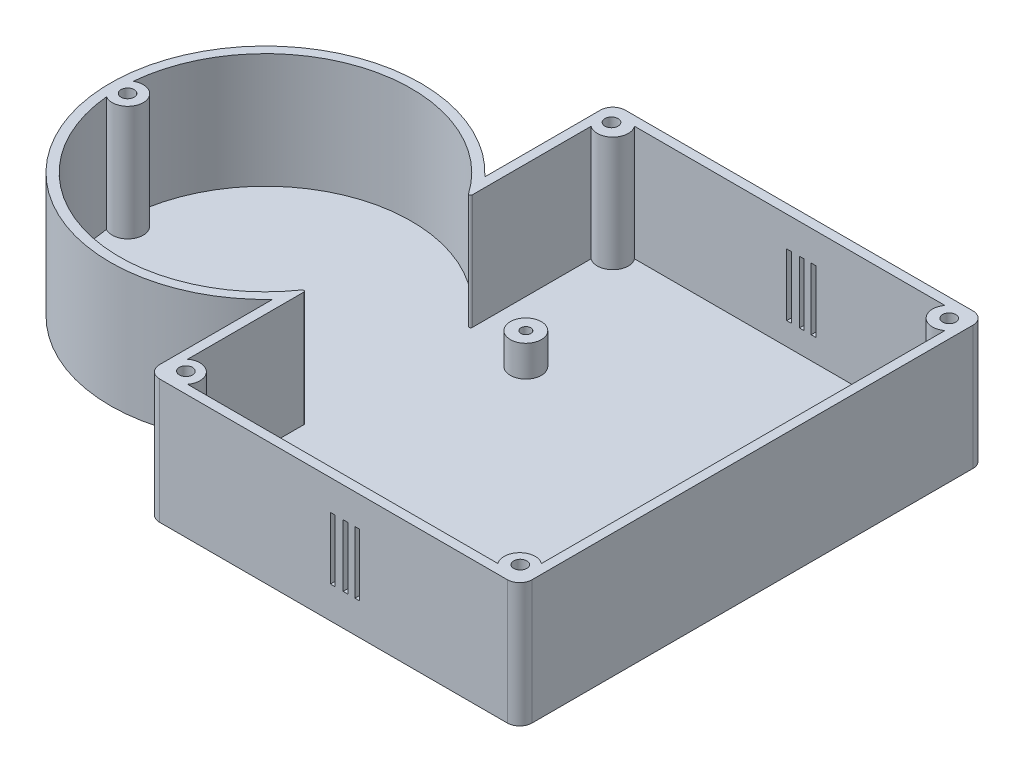
SolidWorks part; units mm, degrees
ref_plane "Front Plane" through (0, 0, 0) normal (0, 0, 1) x (1, 0, 0)
ref_plane "Top Plane" through (0, 0, 0) normal (0, 1, 0) x (1, 0, 0)
ref_plane "Right Plane" through (0, 0, 0) normal (1, 0, 0) x (0, 0, -1)
sketch "Sketch1" plane through (0, 0, 0) normal (0, 1, 0) x (1, 0, 0)
  line L0 (240.8148, 785.6528) -> (1635.5674, 785.6528) construction
sketch "Sketch8" plane through (0, 0, 0) normal (0, 1, 0) x (1, 0, 0)
  line L1 (13.7089, 147.1642) -> (133.7089, 147.1642)
  line L2 (13.7089, 147.1642) -> (13.7089, -2.8358)
  line L3 (13.7089, -2.8358) -> (133.7089, -2.8358)
  line L4 (133.7089, 147.1642) -> (133.7089, -2.8358)
  line L5 (13.7089, 147.1642) -> (133.7089, -2.8358) construction
  line L6 (13.7089, -2.8358) -> (133.7089, 147.1642) construction
  arc A0 (13.7103, 107.7112) -> (14.0464, 36.6131) centre (-21.2814, 71.9959) ccw
  point P0 (73.7089, 72.1642)
  point P5 (73.6501, 72.2835)
  point P6 (-21.2911, 72.0742)
  dimension "D1" = 120
  dimension "D2" = 150
  dimension "D3" = 95
extrude "Boss-Extrude3" add sketch "Sketch8" along normal blind 40 contours L1 L4 L3 L2
sketch "Sketch9" plane through (0, 0, 0) normal (0, 1, 0) x (1, 0, 0)
  circle A0 centre (-22.779, 71.7485) radius 50
extrude "Boss-Extrude4" add sketch "Sketch9" along normal blind 40
shell "Shell1" thickness 3 removed face at (39.2942, 40, -72.0256)
sketch "Sketch11" plane through (0, 0, 0) normal (0, 0, 1) x (1, 0, 0)
  line L5 (72.7415, 30.2907) -> (74.2415, 30.2907)
  line L6 (72.7415, 30.2907) -> (72.7415, 10.2907)
  line L7 (72.7415, 10.2907) -> (74.2415, 10.2907)
  line L8 (74.2415, 30.2907) -> (74.2415, 10.2907)
  line L9 (72.7415, 30.2907) -> (74.2415, 10.2907) construction
  line L10 (72.7415, 10.2907) -> (74.2415, 30.2907) construction
  point P0 (73.4915, 20.2907)
  dimension "D1" = 20
  dimension "D2" = 1.5
sketch "Sketch12" plane through (0, 0, 2.8358) normal (0, 0, 1) x (1, 0, 0)
  line L1 (76.8389, 30.2907) -> (78.3389, 30.2907)
  line L2 (76.8389, 30.2907) -> (76.8389, 10.2907)
  line L3 (76.8389, 10.2907) -> (78.3389, 10.2907)
  line L4 (78.3389, 30.2907) -> (78.3389, 10.2907)
  line L5 (76.8389, 30.2907) -> (78.3389, 10.2907) construction
  line L6 (76.8389, 10.2907) -> (78.3389, 30.2907) construction
  point P0 (77.5889, 20.2907)
  dimension "D1" = 20
  dimension "D2" = 1.5
sketch "Sketch15" plane through (0, 0, 0) normal (0, 0, 1) x (1, 0, 0)
  line L1 (80.6291, 30.2907) -> (82.1291, 30.2907)
  line L2 (80.6291, 30.2907) -> (80.6291, 10.2907)
  line L3 (80.6291, 10.2907) -> (82.1291, 10.2907)
  line L4 (82.1291, 30.2907) -> (82.1291, 10.2907)
  line L5 (80.6291, 30.2907) -> (82.1291, 10.2907) construction
  line L6 (80.6291, 10.2907) -> (82.1291, 30.2907) construction
  point P0 (81.3791, 20.2907)
  dimension "D1" = 1.5
  dimension "D2" = 20
fillet "Fillet2" radius 0.5 2 edges at (16.7089, 21.5, -46.2591) (16.7089, 21.5, -97.2378)
sketch "Sketch17" plane through (1.8488, 3, -2.465) normal (0, 1, 0) x (1, 0, 0)
  circle A0 centre (111.867, 11.1753) radius 5
  circle A5 centre (34.367, 11.1753) radius 5
  circle A6 centre (111.867, 94.1753) radius 5
  circle A7 centre (34.367, 94.1753) radius 5
  dimension "D7" = 83
  dimension "D4" = 77.5
  dimension "D6" = 83
  dimension "D8" = 77.5
extrude "Boss-Extrude6" add sketch "Sketch17" along normal blind 10
sketch "Sketch23" plane through (0, 0, 0) normal (0, 0, 1) x (1, 0, 0)
extrude "Cut-Extrude9" cut sketch "Sketch11" against normal through all both and the other way through all contours L8 L7 L6 L5
extrude "Cut-Extrude10" cut sketch "Sketch12" against normal through all both and the other way through all contours L4 L3 L2 L1
extrude "Cut-Extrude11" cut sketch "Sketch15" against normal through all both and the other way through all contours L4 L3 L2 L1
sketch "Sketch21" plane through (0, 0, 0) normal (0, 0, 1) x (1, 0, 0)
sketch "Sketch27" plane through (0, 0, 0) normal (0, 1, 0) x (1, 0, 0)
sketch "Sketch28" plane through (0, 3, 0) normal (0, 1, 0) x (1, 0, 0)
  line L0 (13.7089, 147.1642) -> (13.7089, 105.9338) construction
  line L1 (13.7089, 147.1642) -> (133.7089, 147.1642) construction
  circle A0 centre (19.7089, 141.1642) radius 5
  dimension "D1" = 6
  dimension "D2" = 6
extrude "Boss-Extrude7" add sketch "Sketch28" along normal blind 37
sketch "Sketch29" plane through (0, 0, 0) normal (0, 1, 0) x (1, 0, 0)
  line L0 (13.7089, 37.5631) -> (13.7089, -2.8358) construction
  line L1 (13.7089, -2.8358) -> (133.7089, -2.8358) construction
  circle A0 centre (19.7089, 3.1642) radius 5
  dimension "D1" = 6
  dimension "D2" = 6
extrude "Boss-Extrude8" add sketch "Sketch29" along normal blind 40
sketch "Sketch30" plane through (0, 0, 0) normal (0, 1, 0) x (1, 0, 0)
  line L0 (133.7089, 147.1642) -> (133.7089, -2.8358) construction
  line L1 (13.7089, 147.1642) -> (133.7089, 147.1642) construction
  circle A0 centre (127.7089, 141.1642) radius 5
  dimension "D1" = 6
  dimension "D2" = 6
extrude "Boss-Extrude9" add sketch "Sketch30" along normal blind 40
sketch "Sketch31" plane through (0, 3, 0) normal (0, 1, 0) x (1, 0, 0)
  line L0 (133.7089, 147.1642) -> (133.7089, -2.8358) construction
  line L1 (13.7089, -2.8358) -> (133.7089, -2.8358) construction
  circle A0 centre (127.7089, 3.1642) radius 5
  dimension "D1" = 6
  dimension "D2" = 6
extrude "Boss-Extrude10" add sketch "Sketch31" along normal blind 37
sketch "Sketch32" plane through (0, 3, 0) normal (0, 1, 0) x (1, 0, 0)
  circle A0 centre (-67.0185, 71.629) radius 5
extrude "Boss-Extrude11" add sketch "Sketch32" along normal blind 37
hole_wizard "#2 (0.221) Diameter Hole1" positions "Sketch34" profile "Sketch35" hole size "#2" standard "ANSI Inch"
sketch "Sketch34" plane through (0, 40, 0) normal (0, 1, 0) x (1, 0, 0)
  point P0 (18.9171, 141.5314)
  point P2 (127.97, 141.2692)
  point P4 (127.6025, 3.4533)
  point P6 (19.7741, 3.5706)
  point P8 (-67.1156, 71.6687)
sketch "Sketch35" plane through (18.9171, 40, -141.5314) normal (1, 0, 0) x (0, 0, 1)
  line L0 (0, 0) -> (0, 9.2768)
  line L1 (0, 9.2768) -> (2.125, 8)
  line L2 (2.125, 8) -> (2.125, 0)
  line L5 (2.125, 0) -> (0, 0)
  line L10 (0, 9.2768) -> (-2.125, 8) construction
  line L11 (0, -6.35) -> (0, 107.95) construction
  dimension "Hole Dia." = 4.25
  dimension "Hole Depth" = 8
  dimension "Drill Angle" = 118
hole_wizard "#2 (0.221) Diameter Hole2" positions "Sketch36" profile "Sketch37" hole size "#2" standard "ANSI Inch"
sketch "Sketch36" plane through (0, 13, 0) normal (0, 1, 0) x (1, 0, 0)
  point P2 (113.8666, 96.6657)
  point P4 (36.2691, 13.6724)
  point P6 (113.8666, 13.4154)
  point P14 (36.2247, 96.6373)
sketch "Sketch37" plane through (113.8666, 13, -96.6657) normal (1, 0, 0) x (0, 0, 1)
  line L0 (0, 0) -> (0, 6.9614)
  line L1 (0, 6.9614) -> (1.6, 6)
  line L2 (1.6, 6) -> (1.6, 0)
  line L5 (1.6, 0) -> (0, 0)
  line L10 (0, 6.9614) -> (-1.6, 6) construction
  line L11 (0, -6.35) -> (0, 107.95) construction
  dimension "Hole Dia." = 3.2
  dimension "Hole Depth" = 6
  dimension "Drill Angle" = 118
fillet "Fillet3" radius 4 4 edges at (133.7089, 20, 2.8358) (133.7089, 20, -147.1642) (13.7089, 20, 2.8358) (13.7089, 20, -147.1642)
